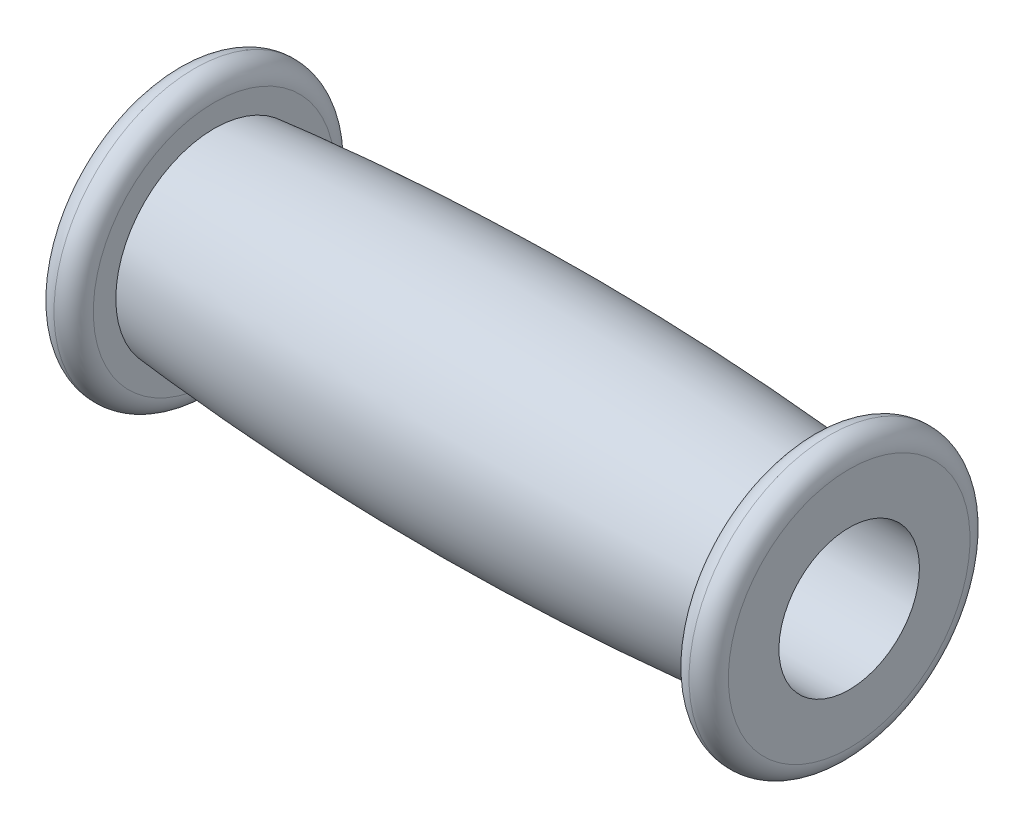
SolidWorks part; units mm, degrees
ref_plane "Front Plane" through (0, 0, 0) normal (0, 0, 1) x (1, 0, 0)
ref_plane "Top Plane" through (0, 0, 0) normal (0, 1, 0) x (1, 0, 0)
ref_plane "Right Plane" through (0, 0, 0) normal (1, 0, 0) x (0, 0, -1)
sketch "Sketch1" plane through (0, 0, 0) normal (0, 0, 1) x (1, 0, 0)
  line L0 (0, 0) -> (0, 25)
  line L1 (0, 25) -> (7, 25)
  line L2 (7, 25) -> (7, 17.5)
  line L3 (7, 17.5) -> (133.6313, 17.5) construction
  line L4 (113, 17.5) -> (113, 25)
  line L5 (113, 25) -> (120, 25)
  line L8 (120, 0) -> (0, 0)
  line L9 (-19.4413, 25) -> (143.6872, 25) construction
  line L10 (120, 25) -> (120, 0)
  line L11 (-29.9832, 20) -> (156.7378, 20) construction
  spline S1 degree 2 poles (7, 17.5) (59.9995, 22.5) (113, 17.5) knots 0 0 0 1 1 1
  point P7 (0, 0)
  point P11 (0, 0)
  dimension "D1" = 25
  dimension "D2" = 7
  dimension "D3" = 120
  dimension "D4" = 7.5
  dimension "D5" = 17.5
  dimension "D6" = 2.5
revolve "Revolve1" add sketch "Sketch1" angle 360 about L8
sketch "Sketch2" plane through (0, 0, 0) normal (-1, 0, 0) x (0, 0, 1)
  circle A0 centre (0, 0) radius 12.5
  dimension "D1" = 25
extrude "Cut-Extrude1" cut sketch "Sketch2" against normal through all
fillet "Fillet2" radius 3.5 4 edges at (120, 25, 0) (113, 25, 0) (7, 25, 0) (0, 25, 0)
